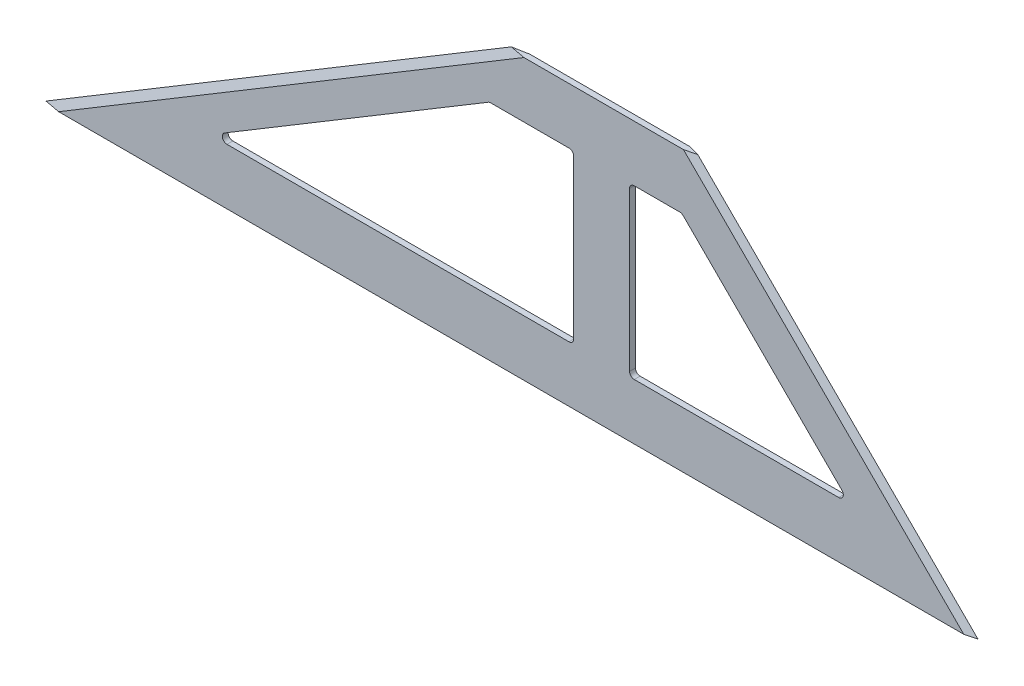
SolidWorks part; units mm, degrees
ref_plane "Front Plane" through (0, 0, 0) normal (0, 0, 1) x (1, 0, 0)
ref_plane "Top Plane" through (0, 0, 0) normal (0, 1, 0) x (1, 0, 0)
ref_plane "Right Plane" through (0, 0, 0) normal (1, 0, 0) x (0, 0, -1)
sketch "Sketch1" plane through (0, 0, 0) normal (0, 0, 1) x (1, 0, 0)
  line L0 (-508, 0) -> (0, 0)
  line L1 (0, 0) -> (-152.7638, 152.4)
  line L2 (-152.7638, 152.4) -> (-254.3638, 152.4)
  line L3 (-254.3638, 152.4) -> (-508, 0)
  line L4 (-508, 0) -> (-508, 192.899)
  line L5 (-244.5005, 152.4) -> (-498.1367, 0) construction
  line L6 (-159.9566, 152.4) -> (-7.1928, 0) construction
  line L7 (-108.3675, 70.5264) -> (-67.1642, 29.4212) construction
  line L8 (-188.3238, 30.48) -> (-68.2255, 30.48)
  line L9 (-264.7477, 121.92) -> (-416.9294, 30.48)
  line L10 (-159.8838, 121.92) -> (-68.2255, 30.48)
  line L11 (-203.5638, 152.4) -> (-203.5638, 0) construction
  line L12 (-218.8038, 121.92) -> (-218.8038, 30.48)
  line L13 (-188.3238, 121.92) -> (-188.3238, 30.48)
  line L14 (-416.9294, 30.48) -> (-218.8038, 30.48)
  line L15 (-188.3238, 121.92) -> (-159.8838, 121.92)
  line L16 (-264.7477, 121.92) -> (-218.8038, 121.92)
  line L17 (-281.9502, 111.5837) -> (-363.4644, 62.605) construction
  line L18 (23.1971, 30.48) -> (-21.4673, 30.48) construction
  line L19 (-43.2082, 121.92) -> (-102.5864, 121.92) construction
  point P23 (-203.5638, 152.4)
  point P30 (-7.1928, 0)
  point P32 (-37.6728, 0)
  point P33 (-498.1367, 0)
  point P35 (-467.6567, 0)
  dimension "D1" = 508
  dimension "D2" = 101.6
  dimension "D3" = 152.4
  dimension "D4" = 59
  dimension "D5" = 5.08
  dimension "D6" = 5.08
  dimension "D7" = 30.48
  dimension "D8" = 30.48
  dimension "D9" = 30.48
  dimension "D10" = 30.48
  dimension "D11" = 30.48
extrude "Boss-Extrude4" add sketch "Sketch1" along normal blind 3.175
fillet "Fillet2" radius 2.54 8 edges at (-68.2255, 30.48, 1.5875) (-188.3238, 30.48, 1.5875) (-188.3238, 121.92, 1.5875) (-159.8838, 121.92, 1.5875) (-416.9294, 30.48, 1.5875) (-218.8038, 30.48, 1.5875) (-264.7477, 121.92, 1.5875) (-218.8038, 121.92, 1.5875)
chamfer "Chamfer1" distance 1.5875 angle 70 2 edges at (-381.1819, 76.2, 0) (-76.3819, 76.2, 0) first distance on face at (-381.1819, 76.2, 1.5875) first distance on face at (-76.3819, 76.2, 1.5875)
chamfer "Chamfer2" distance 1.5875 angle 70 2 edges at (-76.3819, 76.2, 3.175) (-381.1819, 76.2, 3.175) first distance on face at (-76.3819, 76.2, 2.3812) first distance on face at (-381.1819, 76.2, 2.3812)
